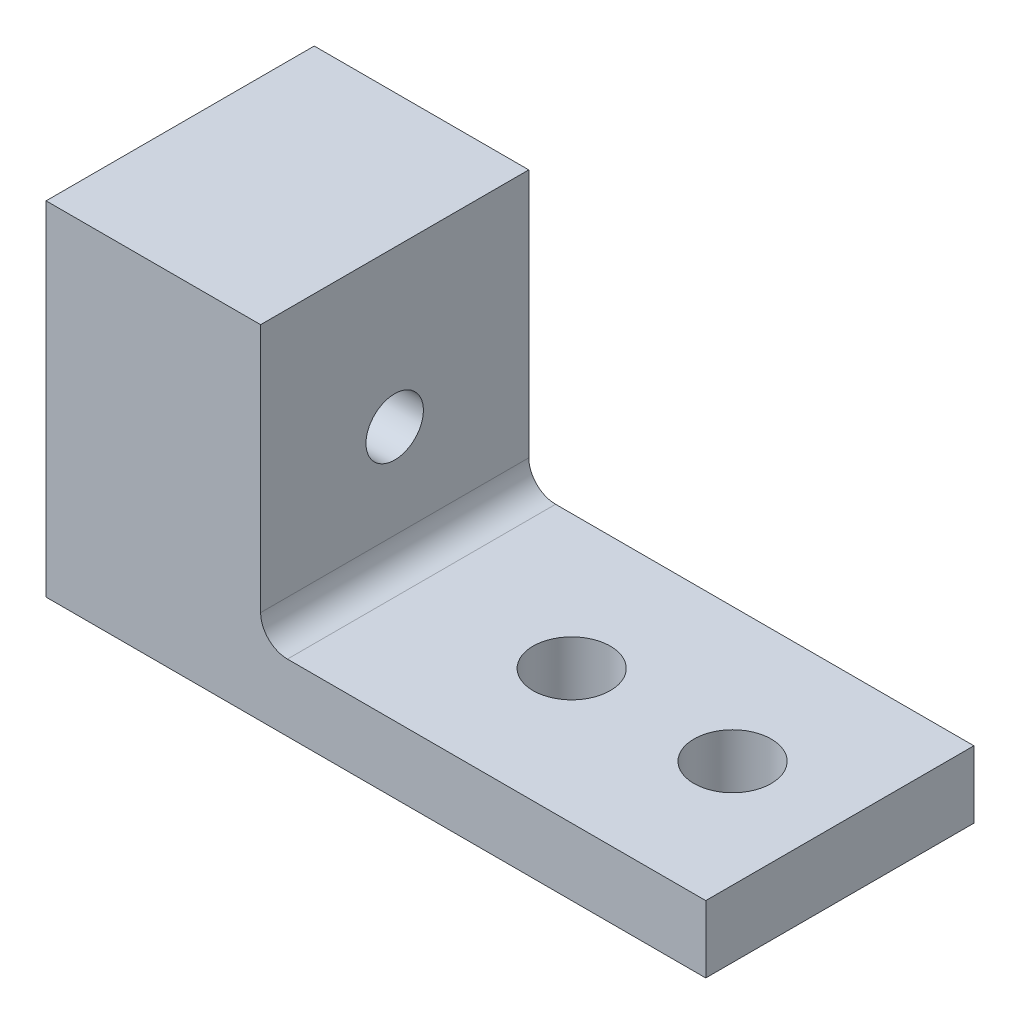
SolidWorks part; units mm, degrees
material "Plain Carbon Steel"
ref_plane "Front Plane" through (0, 0, 0) normal (0, 0, 1) x (1, 0, 0)
ref_plane "Top Plane" through (0, 0, 0) normal (0, 1, 0) x (1, 0, 0)
ref_plane "Right Plane" through (0, 0, 0) normal (1, 0, 0) x (0, 0, -1)
sketch "Sketch1" plane through (0, 0, 0) normal (0, 0, 1) x (1, 0, 0)
  line L0 (0, 0) -> (0, 16.256)
  line L1 (0, 16.256) -> (10.16, 16.256)
  line L2 (10.16, 16.256) -> (10.16, 3.175)
  line L3 (10.16, 3.175) -> (31.242, 3.175)
  line L4 (31.242, 3.175) -> (31.242, 0)
  line L5 (31.242, 0) -> (0, 0)
  dimension "D1" = 10.16
  dimension "D2" = 3.175
  dimension "D4" = 16.256
  dimension "D3" = 21.082
extrude "Boss-Extrude1" add sketch "Sketch1" against normal mid plane 12.7
sketch "Sketch2" plane through (0, 0, 0) normal (-1, 0, 0) x (0, 0, 1)
  circle A0 centre (0, 8.89) radius 1.3589
  dimension "D1" = 2.7178
  dimension "D2" = 8.89
extrude "Cut-Extrude1" cut sketch "Sketch2" against normal up to next
sketch "Sketch3" plane through (0, 0, 0) normal (0, -1, 0) x (1, 0, 0)
  circle A0 centre (18.542, 0) radius 1.8288
  dimension "D1" = 3.6576
  dimension "D2" = 8.382
extrude "Cut-Extrude2" cut sketch "Sketch3" against normal up to next
fillet "Fillet2" radius 1.27 1 edges at (10.16, 3.175, 0)
pattern_linear "LPattern1" count 2 spacing 7.62 along (1, 0, 0) of "Cut-Extrude2"
equation "\"D2@Sketch1\"=1/8"
equation "\"Middle Coupler Inner Daimeter\"= 3.875in"
equation "\"Middle Coupler  Wall Thickness\" = 0.25in"
equation "\"Middle Coupler Bottom Thickness\"= 0.2in"
equation "\"Bearing Rail Offset\"= 0.45in"
equation "\"3-56 UNF Tap\"= 0.089in"
equation "\"3-48 Tap\"= 0.079in"
equation "\"3-56 UNF Clearance\"= 0.104in"
equation "\"3-48 Clearance\" = 0.104in"
equation "\"Ball Bearing Distance\"= 0.03in"
equation "\"TCA Outer Diameter\" = 6in"
equation "\"Interstage Aeroframe Wall Thickness\" = 0.072in"
equation "\"Compression Spring OD\"= 0.42in"
equation "\"10-24 Tap\"= 0.157in"
equation "\"10-24 Clearance\"= 0.196in"
equation "\"Lower Stage Fuselage Wall Thickness\" = 0.25in"
equation "\"6-32 Tap\" = 0.107in"
equation "\"6-32 Clearance\" = 0.144"
equation "\"1/4-20 Tap\" = 0.201in"
equation "\"12-24 Tap\" = 0.177in"
equation "\"12-24 Major Diameter\"= 0.216in"
equation "\"D1@Sketch2\"=\"6-32 Tap\""
equation "\"D1@Sketch3\"=\"6-32 Clearance\""
